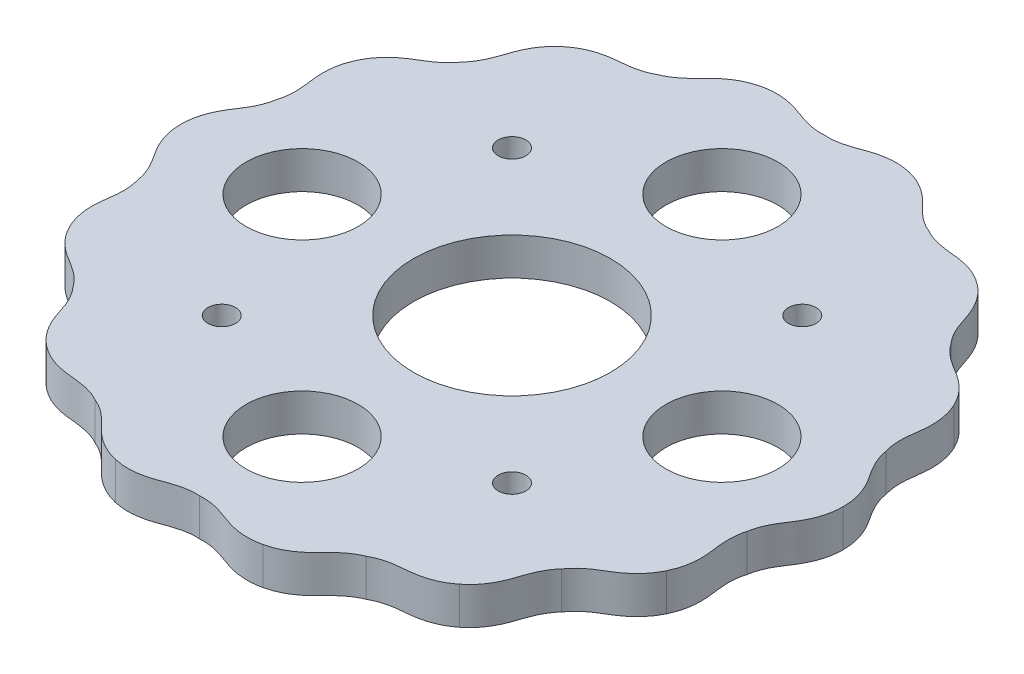
SolidWorks part; units mm, degrees
ref_plane "Front Plane" through (0, 0, 0) normal (0, 0, 1) x (1, 0, 0)
ref_plane "Top Plane" through (0, 0, 0) normal (0, 1, 0) x (1, 0, 0)
ref_plane "Right Plane" through (0, 0, 0) normal (1, 0, 0) x (0, 0, -1)
sketch "Sketch1" plane through (0, 0, 0) normal (0, 1, 0) x (1, 0, 0)
  line L0 (0, 0) -> (37.5, 0) construction
  line L1 (0, 0) -> (37.4807, 1.2019) construction
  line L2 (0, 0) -> (37.423, 2.4026) construction
  line L3 (0, 0) -> (37.3267, 3.6009) construction
  line L4 (0, 0) -> (37.1921, 4.7954) construction
  line L5 (0, 0) -> (37.0193, 5.985) construction
  line L6 (0, 0) -> (36.8085, 7.1684) construction
  line L7 (0, 0) -> (36.5598, 8.3445) construction
  line L8 (0, 0) -> (36.2736, 9.512) construction
  line L9 (0, 0) -> (35.95, 10.6698) construction
  line L10 (0, 0) -> (35.5896, 11.8166) construction
  line L11 (0, 0) -> (35.1926, 12.9512) construction
  line L12 (0, 0) -> (34.7594, 14.0725) construction
  line L13 (0, 0) -> (34.2905, 15.1794) construction
  line L14 (0, 0) -> (33.7863, 16.2706) construction
  line L15 (37.5, 0) -> (38.5, 0) construction
  line L16 (37.4807, 1.2019) -> (38.3521, 1.6927) construction
  line L17 (37.423, 2.4026) -> (37.9413, 3.2578) construction
  line L18 (37.3267, 3.6009) -> (37.3588, 4.6003) construction
  line L19 (37.1921, 4.7954) -> (36.7296, 5.682) construction
  line L20 (37.0193, 5.985) -> (36.1812, 6.5305) construction
  line L21 (36.8085, 7.1684) -> (35.8105, 7.2325) construction
  line L22 (36.5598, 8.3445) -> (35.5849, 8.122) construction
  line L23 (37, 0.0019) -> (37, 0)
  line L24 (33.3367, 16.052) -> (33.3358, 16.0537)
  line L25 (37, -0.0019) -> (37, 0)
  line L26 (33.3367, -16.052) -> (33.3358, -16.0537)
  line L27 (33.335, -16.0554) -> (33.3358, -16.0537)
  line L28 (23.0706, -28.9266) -> (23.0691, -28.9278)
  line L29 (23.0677, -28.9289) -> (23.0691, -28.9278)
  line L30 (8.2351, -36.0719) -> (8.2333, -36.0723)
  line L31 (8.2315, -36.0727) -> (8.2333, -36.0723)
  line L32 (-8.2315, -36.0727) -> (-8.2333, -36.0723)
  line L33 (-8.2351, -36.0719) -> (-8.2333, -36.0723)
  line L34 (-23.0677, -28.9289) -> (-23.0691, -28.9278)
  line L35 (-23.0706, -28.9266) -> (-23.0691, -28.9278)
  line L36 (-33.335, -16.0554) -> (-33.3358, -16.0537)
  line L37 (-33.3367, -16.052) -> (-33.3358, -16.0537)
  line L38 (-37, -0.0019) -> (-37, 0)
  line L39 (-37, 0.0019) -> (-37, 0)
  line L40 (-33.3367, 16.052) -> (-33.3358, 16.0537)
  line L41 (-33.335, 16.0554) -> (-33.3358, 16.0537)
  line L42 (-23.0706, 28.9266) -> (-23.0691, 28.9278)
  line L43 (-23.0677, 28.9289) -> (-23.0691, 28.9278)
  line L44 (-8.2351, 36.0719) -> (-8.2333, 36.0723)
  line L45 (-8.2315, 36.0727) -> (-8.2333, 36.0723)
  line L46 (8.2315, 36.0727) -> (8.2333, 36.0723)
  line L47 (8.2351, 36.0719) -> (8.2333, 36.0723)
  line L48 (23.0677, 28.9289) -> (23.0691, 28.9278)
  line L49 (23.0706, 28.9266) -> (23.0691, 28.9278)
  line L50 (33.335, 16.0554) -> (33.3358, 16.0537)
  line L51 (35.5, 0.0037) -> (35.5, 0)
  line L52 (31.986, 15.3995) -> (31.9844, 15.4029)
  line L53 (35.5, -0.0037) -> (35.5, 0)
  line L54 (31.986, -15.3995) -> (31.9844, -15.4029)
  line L55 (31.9828, -15.4062) -> (31.9844, -15.4029)
  line L56 (22.1368, -27.7527) -> (22.1339, -27.755)
  line L57 (22.131, -27.7573) -> (22.1339, -27.755)
  line L58 (7.9031, -34.6091) -> (7.8995, -34.6099)
  line L59 (7.8959, -34.6108) -> (7.8995, -34.6099)
  line L60 (-7.8959, -34.6108) -> (-7.8995, -34.6099)
  line L61 (-7.9031, -34.6091) -> (-7.8995, -34.6099)
  line L62 (-22.131, -27.7573) -> (-22.1339, -27.755)
  line L63 (-22.1368, -27.7527) -> (-22.1339, -27.755)
  line L64 (-31.9828, -15.4062) -> (-31.9844, -15.4029)
  line L65 (-31.986, -15.3995) -> (-31.9844, -15.4029)
  line L66 (-35.5, -0.0037) -> (-35.5, 0)
  line L67 (-35.5, 0.0037) -> (-35.5, 0)
  line L68 (-31.986, 15.3995) -> (-31.9844, 15.4029)
  line L69 (-31.9828, 15.4062) -> (-31.9844, 15.4029)
  line L70 (-22.1368, 27.7527) -> (-22.1339, 27.755)
  line L71 (-22.131, 27.7573) -> (-22.1339, 27.755)
  line L72 (-7.9031, 34.6091) -> (-7.8995, 34.6099)
  line L73 (-7.8959, 34.6108) -> (-7.8995, 34.6099)
  line L74 (7.8959, 34.6108) -> (7.8995, 34.6099)
  line L75 (7.9031, 34.6091) -> (7.8995, 34.6099)
  line L76 (22.131, 27.7573) -> (22.1339, 27.755)
  line L77 (22.1368, 27.7527) -> (22.1339, 27.755)
  line L78 (31.9828, 15.4062) -> (31.9844, 15.4029)
  circle A0 centre (0, 0) radius 35 construction
  circle A1 centre (37.5, 0) radius 2.5 construction
  circle A2 centre (0, 0) radius 37.5 construction
  spline S0 degree 3 poles (35.5849, 8.122) (35.6266, 7.5364) (36.0345, 6.7125) (36.7836, 5.6218) (37.4152, 4.5501) (38.2239, 2.702) (38.5014, 1.1074) (38.5, 0) knots 0 0 0 0 0.195516 0.310928 0.453873 0.621058 1 1 1 1
  spline S1 degree 3 poles (35.5849, 8.122) (35.3683, 8.6678) (35.3784, 9.5871) (35.5801, 10.8948) (35.6841, 12.1344) (35.611, 14.1503) (35.169, 15.7074) (34.6873, 16.7045) knots 0 0 0 0 0.195516 0.310928 0.453873 0.621058 1 1 1 1
  spline S2 degree 1 poles (34.1119, 7.7858) (33.3367, 16.052) knots 0 0 1 1 construction
  spline S3 degree 1 poles (34.1119, 7.7858) (37, 0.0019) knots 0 0 1 1 construction
  spline S4 degree 3 poles (33.3367, 16.052) (33.6005, 15.5058) (33.9037, 14.6401) (34.1146, 13.4372) (34.174, 12.5211) (34.1413, 11.5771) (34.0239, 10.6392) (33.8823, 9.6155) (33.9055, 8.625) (34.0243, 8.0514) (34.1119, 7.7858) knots 0.015853 0.015853 0.015853 0.015853 0.26189 0.384908 0.507927 0.630945 0.753963 0.876982 0.938491 1 1 1 1
  spline S5 degree 3 poles (34.1119, 7.7858) (34.1483, 7.5085) (34.2901, 6.9402) (34.6989, 6.0377) (35.2706, 5.1769) (35.7834, 4.3828) (36.2224, 3.5464) (36.5664, 2.6953) (36.8983, 1.52) (37.0008, 0.6085) (37, 0.0019) knots 0.015853 0.015853 0.015853 0.015853 0.077362 0.138872 0.26189 0.384908 0.507927 0.630945 0.753963 1 1 1 1
  spline S6 degree 3 poles (37, -0.0019) (37.0008, -0.6085) (36.8983, -1.52) (36.5664, -2.6953) (36.2224, -3.5464) (35.7834, -4.3828) (35.2706, -5.1769) (34.6989, -6.0377) (34.2901, -6.9402) (34.1483, -7.5085) (34.1119, -7.7858) knots 0.015853 0.015853 0.015853 0.015853 0.26189 0.384908 0.507927 0.630945 0.753963 0.876982 0.938491 1 1 1 1
  spline S7 degree 3 poles (34.1119, -7.7858) (34.0243, -8.0514) (33.9055, -8.625) (33.8823, -9.6155) (34.0239, -10.6392) (34.1413, -11.5771) (34.174, -12.5211) (34.1146, -13.4372) (33.9037, -14.6401) (33.6005, -15.5058) (33.3367, -16.052) knots 0.015853 0.015853 0.015853 0.015853 0.077362 0.138872 0.26189 0.384908 0.507927 0.630945 0.753963 1 1 1 1
  spline S8 degree 3 poles (33.335, -16.0554) (33.0725, -16.6022) (32.5847, -17.3791) (31.7758, -18.2939) (31.0965, -18.9115) (30.3381, -19.4746) (29.5316, -19.9675) (28.6429, -20.4951) (27.8831, -21.1308) (27.5087, -21.5813) (27.3556, -21.8154) knots 0.015853 0.015853 0.015853 0.015853 0.26189 0.384908 0.507927 0.630945 0.753963 0.876982 0.938491 1 1 1 1
  spline S9 degree 3 poles (27.3556, -21.8154) (27.1615, -22.0167) (26.8056, -22.4819) (26.3549, -23.3642) (26.0383, -24.348) (25.7371, -25.2439) (25.357, -26.1087) (24.906, -26.9083) (24.1941, -27.9005) (23.5453, -28.549) (23.0706, -28.9266) knots 0.015853 0.015853 0.015853 0.015853 0.077362 0.138872 0.26189 0.384908 0.507927 0.630945 0.753963 1 1 1 1
  spline S10 degree 3 poles (23.0677, -28.9289) (22.5939, -29.3077) (21.8173, -29.796) (20.6915, -30.2693) (19.8116, -30.531) (18.884, -30.7092) (17.9435, -30.8034) (16.9139, -30.8931) (15.9535, -31.1362) (15.4207, -31.3797) (15.1812, -31.5241) knots 0.015853 0.015853 0.015853 0.015853 0.26189 0.384908 0.507927 0.630945 0.753963 0.876982 0.938491 1 1 1 1
  spline S11 degree 3 poles (15.1812, -31.5241) (14.919, -31.6213) (14.3964, -31.886) (13.6076, -32.4854) (12.8955, -33.2344) (12.2354, -33.9109) (11.5177, -34.5251) (10.7645, -35.0499) (9.6926, -35.6349) (8.8266, -35.9377) (8.2351, -36.0719) knots 0.015853 0.015853 0.015853 0.015853 0.077362 0.138872 0.26189 0.384908 0.507927 0.630945 0.753963 1 1 1 1
  spline S12 degree 3 poles (8.2315, -36.0727) (7.6402, -36.2085) (6.7287, -36.3114) (5.5091, -36.2494) (4.6028, -36.1034) (3.6897, -35.8614) (2.8014, -35.5383) (1.8349, -35.1724) (0.8641, -34.9747) (0.2785, -34.9629) (0, -34.9891) knots 0.015853 0.015853 0.015853 0.015853 0.26189 0.384908 0.507927 0.630945 0.753963 0.876982 0.938491 1 1 1 1
  spline S13 degree 3 poles (0, -34.9891) (-0.2785, -34.9629) (-0.8641, -34.9747) (-1.8349, -35.1724) (-2.8014, -35.5383) (-3.6897, -35.8614) (-4.6028, -36.1034) (-5.5091, -36.2494) (-6.7287, -36.3114) (-7.6402, -36.2085) (-8.2315, -36.0727) knots 0.015853 0.015853 0.015853 0.015853 0.077362 0.138872 0.26189 0.384908 0.507927 0.630945 0.753963 1 1 1 1
  spline S14 degree 3 poles (-8.2351, -36.0719) (-8.8266, -35.9377) (-9.6926, -35.6349) (-10.7645, -35.0499) (-11.5177, -34.5251) (-12.2354, -33.9109) (-12.8955, -33.2344) (-13.6076, -32.4854) (-14.3964, -31.886) (-14.919, -31.6213) (-15.1812, -31.5241) knots 0.015853 0.015853 0.015853 0.015853 0.26189 0.384908 0.507927 0.630945 0.753963 0.876982 0.938491 1 1 1 1
  spline S15 degree 3 poles (-15.1812, -31.5241) (-15.4207, -31.3797) (-15.9535, -31.1362) (-16.9139, -30.8931) (-17.9435, -30.8034) (-18.884, -30.7092) (-19.8116, -30.531) (-20.6915, -30.2693) (-21.8173, -29.796) (-22.5939, -29.3077) (-23.0677, -28.9289) knots 0.015853 0.015853 0.015853 0.015853 0.077362 0.138872 0.26189 0.384908 0.507927 0.630945 0.753963 1 1 1 1
  spline S16 degree 3 poles (-23.0706, -28.9266) (-23.5453, -28.549) (-24.1941, -27.9005) (-24.906, -26.9083) (-25.357, -26.1087) (-25.7371, -25.2439) (-26.0383, -24.348) (-26.3549, -23.3642) (-26.8056, -22.4819) (-27.1615, -22.0167) (-27.3556, -21.8154) knots 0.015853 0.015853 0.015853 0.015853 0.26189 0.384908 0.507927 0.630945 0.753963 0.876982 0.938491 1 1 1 1
  spline S17 degree 3 poles (-27.3556, -21.8154) (-27.5087, -21.5813) (-27.8831, -21.1308) (-28.6429, -20.4951) (-29.5316, -19.9675) (-30.3381, -19.4746) (-31.0965, -18.9115) (-31.7758, -18.2939) (-32.5847, -17.3791) (-33.0725, -16.6022) (-33.335, -16.0554) knots 0.015853 0.015853 0.015853 0.015853 0.077362 0.138872 0.26189 0.384908 0.507927 0.630945 0.753963 1 1 1 1
  spline S18 degree 3 poles (-33.3367, -16.052) (-33.6005, -15.5058) (-33.9037, -14.6401) (-34.1146, -13.4372) (-34.174, -12.5211) (-34.1413, -11.5771) (-34.0239, -10.6392) (-33.8823, -9.6155) (-33.9055, -8.625) (-34.0243, -8.0514) (-34.1119, -7.7858) knots 0.015853 0.015853 0.015853 0.015853 0.26189 0.384908 0.507927 0.630945 0.753963 0.876982 0.938491 1 1 1 1
  spline S19 degree 3 poles (-34.1119, -7.7858) (-34.1483, -7.5085) (-34.2901, -6.9402) (-34.6989, -6.0377) (-35.2706, -5.1769) (-35.7834, -4.3828) (-36.2224, -3.5464) (-36.5664, -2.6953) (-36.8983, -1.52) (-37.0008, -0.6085) (-37, -0.0019) knots 0.015853 0.015853 0.015853 0.015853 0.077362 0.138872 0.26189 0.384908 0.507927 0.630945 0.753963 1 1 1 1
  spline S20 degree 3 poles (-37, 0.0019) (-37.0008, 0.6085) (-36.8983, 1.52) (-36.5664, 2.6953) (-36.2224, 3.5464) (-35.7834, 4.3828) (-35.2706, 5.1769) (-34.6989, 6.0377) (-34.2901, 6.9402) (-34.1483, 7.5085) (-34.1119, 7.7858) knots 0.015853 0.015853 0.015853 0.015853 0.26189 0.384908 0.507927 0.630945 0.753963 0.876982 0.938491 1 1 1 1
  spline S21 degree 3 poles (-34.1119, 7.7858) (-34.0243, 8.0514) (-33.9055, 8.625) (-33.8823, 9.6155) (-34.0239, 10.6392) (-34.1413, 11.5771) (-34.174, 12.5211) (-34.1146, 13.4372) (-33.9037, 14.6401) (-33.6005, 15.5058) (-33.3367, 16.052) knots 0.015853 0.015853 0.015853 0.015853 0.077362 0.138872 0.26189 0.384908 0.507927 0.630945 0.753963 1 1 1 1
  spline S22 degree 3 poles (-33.335, 16.0554) (-33.0725, 16.6022) (-32.5847, 17.3791) (-31.7758, 18.2939) (-31.0965, 18.9115) (-30.3381, 19.4746) (-29.5316, 19.9675) (-28.6429, 20.4951) (-27.8831, 21.1308) (-27.5087, 21.5813) (-27.3556, 21.8154) knots 0.015853 0.015853 0.015853 0.015853 0.26189 0.384908 0.507927 0.630945 0.753963 0.876982 0.938491 1 1 1 1
  spline S23 degree 3 poles (-27.3556, 21.8154) (-27.1615, 22.0167) (-26.8056, 22.4819) (-26.3549, 23.3642) (-26.0383, 24.348) (-25.7371, 25.2439) (-25.357, 26.1087) (-24.906, 26.9083) (-24.1941, 27.9005) (-23.5453, 28.549) (-23.0706, 28.9266) knots 0.015853 0.015853 0.015853 0.015853 0.077362 0.138872 0.26189 0.384908 0.507927 0.630945 0.753963 1 1 1 1
  spline S24 degree 3 poles (-23.0677, 28.9289) (-22.5939, 29.3077) (-21.8173, 29.796) (-20.6915, 30.2693) (-19.8116, 30.531) (-18.884, 30.7092) (-17.9435, 30.8034) (-16.9139, 30.8931) (-15.9535, 31.1362) (-15.4207, 31.3797) (-15.1812, 31.5241) knots 0.015853 0.015853 0.015853 0.015853 0.26189 0.384908 0.507927 0.630945 0.753963 0.876982 0.938491 1 1 1 1
  spline S25 degree 3 poles (-15.1812, 31.5241) (-14.919, 31.6213) (-14.3964, 31.886) (-13.6076, 32.4854) (-12.8955, 33.2344) (-12.2354, 33.9109) (-11.5177, 34.5251) (-10.7645, 35.0499) (-9.6926, 35.6349) (-8.8266, 35.9377) (-8.2351, 36.0719) knots 0.015853 0.015853 0.015853 0.015853 0.077362 0.138872 0.26189 0.384908 0.507927 0.630945 0.753963 1 1 1 1
  spline S26 degree 3 poles (-8.2315, 36.0727) (-7.6402, 36.2085) (-6.7287, 36.3114) (-5.5091, 36.2494) (-4.6028, 36.1034) (-3.6897, 35.8614) (-2.8014, 35.5383) (-1.8349, 35.1724) (-0.8641, 34.9747) (-0.2785, 34.9629) (0, 34.9891) knots 0.015853 0.015853 0.015853 0.015853 0.26189 0.384908 0.507927 0.630945 0.753963 0.876982 0.938491 1 1 1 1
  spline S27 degree 3 poles (0, 34.9891) (0.2785, 34.9629) (0.8641, 34.9747) (1.8349, 35.1724) (2.8014, 35.5383) (3.6897, 35.8614) (4.6028, 36.1034) (5.5091, 36.2494) (6.7287, 36.3114) (7.6402, 36.2085) (8.2315, 36.0727) knots 0.015853 0.015853 0.015853 0.015853 0.077362 0.138872 0.26189 0.384908 0.507927 0.630945 0.753963 1 1 1 1
  spline S28 degree 3 poles (8.2351, 36.0719) (8.8266, 35.9377) (9.6926, 35.6349) (10.7645, 35.0499) (11.5177, 34.5251) (12.2354, 33.9109) (12.8955, 33.2344) (13.6076, 32.4854) (14.3964, 31.886) (14.919, 31.6213) (15.1812, 31.5241) knots 0.015853 0.015853 0.015853 0.015853 0.26189 0.384908 0.507927 0.630945 0.753963 0.876982 0.938491 1 1 1 1
  spline S29 degree 3 poles (15.1812, 31.5241) (15.4207, 31.3797) (15.9535, 31.1362) (16.9139, 30.8931) (17.9435, 30.8034) (18.884, 30.7092) (19.8116, 30.531) (20.6915, 30.2693) (21.8173, 29.796) (22.5939, 29.3077) (23.0677, 28.9289) knots 0.015853 0.015853 0.015853 0.015853 0.077362 0.138872 0.26189 0.384908 0.507927 0.630945 0.753963 1 1 1 1
  spline S30 degree 3 poles (23.0706, 28.9266) (23.5453, 28.549) (24.1941, 27.9005) (24.906, 26.9083) (25.357, 26.1087) (25.7371, 25.2439) (26.0383, 24.348) (26.3549, 23.3642) (26.8056, 22.4819) (27.1615, 22.0167) (27.3556, 21.8154) knots 0.015853 0.015853 0.015853 0.015853 0.26189 0.384908 0.507927 0.630945 0.753963 0.876982 0.938491 1 1 1 1
  spline S31 degree 3 poles (27.3556, 21.8154) (27.5087, 21.5813) (27.8831, 21.1308) (28.6429, 20.4951) (29.5316, 19.9675) (30.3381, 19.4746) (31.0965, 18.9115) (31.7758, 18.2939) (32.5847, 17.3791) (33.0725, 16.6022) (33.335, 16.0554) knots 0.015853 0.015853 0.015853 0.015853 0.077362 0.138872 0.26189 0.384908 0.507927 0.630945 0.753963 1 1 1 1
  spline S32 degree 1 poles (32.6448, 7.451) (35.5, 0.0037) knots 0 0 1 1 construction
  spline S33 degree 1 poles (32.6448, 7.451) (31.986, 15.3995) knots 0 0 1 1 construction
  spline S34 degree 3 poles (35.5, 0.0037) (35.5006, 0.4959) (35.4183, 1.2336) (35.1496, 2.1927) (34.8707, 2.8896) (34.4997, 3.6015) (34.1394, 4.1652) (33.6939, 4.8394) (33.3068, 5.4873) (32.9751, 6.1975) (32.758, 6.8733) (32.6748, 7.2607) (32.6448, 7.451) knots 0.023011 0.023011 0.023011 0.023011 0.267258 0.389382 0.511505 0.633629 0.755753 0.816814 0.877876 0.938938 0.969469 1 1 1 1
  spline S35 degree 3 poles (32.6448, 7.451) (32.5893, 7.6354) (32.4961, 8.0206) (32.3985, 8.7236) (32.3893, 9.5074) (32.4569, 10.2591) (32.5657, 11.0598) (32.6458, 11.724) (32.6712, 12.5264) (32.6201, 13.2752) (32.446, 14.256) (32.2001, 14.9563) (31.986, 15.3995) knots 0.023011 0.023011 0.023011 0.023011 0.053542 0.084072 0.145134 0.206196 0.267258 0.389382 0.511505 0.633629 0.755753 1 1 1 1
  spline S36 degree 3 poles (32.6448, -7.451) (32.6748, -7.2607) (32.758, -6.8733) (32.9751, -6.1975) (33.3068, -5.4873) (33.6939, -4.8394) (34.1394, -4.1652) (34.4997, -3.6015) (34.8707, -2.8896) (35.1496, -2.1927) (35.4183, -1.2336) (35.5006, -0.4959) (35.5, -0.0037) knots 0.023011 0.023011 0.023011 0.023011 0.053542 0.084072 0.145134 0.206196 0.267258 0.389382 0.511505 0.633629 0.755753 1 1 1 1
  spline S37 degree 3 poles (31.986, -15.3995) (32.2001, -14.9563) (32.446, -14.256) (32.6201, -13.2752) (32.6712, -12.5264) (32.6458, -11.724) (32.5657, -11.0598) (32.4569, -10.2591) (32.3893, -9.5074) (32.3985, -8.7236) (32.4961, -8.0206) (32.5893, -7.6354) (32.6448, -7.451) knots 0.023011 0.023011 0.023011 0.023011 0.267258 0.389382 0.511505 0.633629 0.755753 0.816814 0.877876 0.938938 0.969469 1 1 1 1
  spline S38 degree 3 poles (26.1791, -20.8771) (26.2887, -20.7187) (26.5317, -20.4057) (27.0205, -19.8911) (27.6275, -19.3952) (28.2574, -18.9793) (28.9513, -18.5652) (29.5206, -18.2137) (30.1637, -17.7333) (30.7173, -17.2264) (31.3755, -16.4789) (31.7698, -15.8499) (31.9828, -15.4062) knots 0.023011 0.023011 0.023011 0.023011 0.053542 0.084072 0.145134 0.206196 0.267258 0.389382 0.511505 0.633629 0.755753 1 1 1 1
  spline S39 degree 3 poles (22.1368, -27.7527) (22.522, -27.4463) (23.0474, -26.922) (23.6297, -26.1139) (24.0007, -25.4614) (24.326, -24.7275) (24.542, -24.0943) (24.7914, -23.3257) (25.0566, -22.619) (25.405, -21.9169) (25.798, -21.3258) (26.0491, -21.0192) (26.1791, -20.8771) knots 0.023011 0.023011 0.023011 0.023011 0.267258 0.389382 0.511505 0.633629 0.755753 0.816814 0.877876 0.938938 0.969469 1 1 1 1
  spline S40 degree 3 poles (14.5283, -30.1683) (14.6957, -30.0732) (15.0505, -29.8966) (15.7143, -29.645) (16.4763, -29.4616) (17.2242, -29.3602) (18.0291, -29.2882) (18.6945, -29.2185) (19.4823, -29.0647) (20.201, -28.8482) (21.1184, -28.4603) (21.7465, -28.0647) (22.131, -27.7573) knots 0.023011 0.023011 0.023011 0.023011 0.053542 0.084072 0.145134 0.206196 0.267258 0.389382 0.511505 0.633629 0.755753 1 1 1 1
  spline S41 degree 3 poles (7.9031, -34.6091) (8.3831, -34.5002) (9.084, -34.2557) (9.9593, -33.7804) (10.5766, -33.3534) (11.1881, -32.8334) (11.6575, -32.3566) (12.2156, -31.7723) (12.7612, -31.2507) (13.3797, -30.7693) (13.9903, -30.4072) (14.3495, -30.2399) (14.5283, -30.1683) knots 0.023011 0.023011 0.023011 0.023011 0.267258 0.389382 0.511505 0.633629 0.755753 0.816814 0.877876 0.938938 0.969469 1 1 1 1
  spline S42 degree 3 poles (0, -33.4843) (0.1922, -33.4712) (0.5884, -33.4661) (1.2956, -33.5274) (2.0617, -33.6928) (2.7796, -33.926) (3.536, -34.2103) (4.1657, -34.4362) (4.9423, -34.6394) (5.6838, -34.7562) (6.6786, -34.8048) (7.4161, -34.7209) (7.8959, -34.6108) knots 0.023011 0.023011 0.023011 0.023011 0.053542 0.084072 0.145134 0.206196 0.267258 0.389382 0.511505 0.633629 0.755753 1 1 1 1
  spline S43 degree 3 poles (-7.8959, -34.6108) (-7.4161, -34.7209) (-6.6786, -34.8048) (-5.6838, -34.7562) (-4.9423, -34.6394) (-4.1657, -34.4362) (-3.536, -34.2103) (-2.7796, -33.926) (-2.0617, -33.6928) (-1.2956, -33.5274) (-0.5884, -33.4661) (-0.1922, -33.4712) (0, -33.4843) knots 0.023011 0.023011 0.023011 0.023011 0.267258 0.389382 0.511505 0.633629 0.755753 0.816814 0.877876 0.938938 0.969469 1 1 1 1
  spline S44 degree 3 poles (-14.5283, -30.1683) (-14.3495, -30.2399) (-13.9903, -30.4072) (-13.3797, -30.7693) (-12.7612, -31.2507) (-12.2156, -31.7723) (-11.6575, -32.3566) (-11.1881, -32.8334) (-10.5766, -33.3534) (-9.9593, -33.7804) (-9.084, -34.2557) (-8.3831, -34.5002) (-7.9031, -34.6091) knots 0.023011 0.023011 0.023011 0.023011 0.053542 0.084072 0.145134 0.206196 0.267258 0.389382 0.511505 0.633629 0.755753 1 1 1 1
  spline S45 degree 3 poles (-22.131, -27.7573) (-21.7465, -28.0647) (-21.1184, -28.4603) (-20.201, -28.8482) (-19.4823, -29.0647) (-18.6945, -29.2185) (-18.0291, -29.2882) (-17.2242, -29.3602) (-16.4763, -29.4616) (-15.7143, -29.645) (-15.0505, -29.8966) (-14.6957, -30.0732) (-14.5283, -30.1683) knots 0.023011 0.023011 0.023011 0.023011 0.267258 0.389382 0.511505 0.633629 0.755753 0.816814 0.877876 0.938938 0.969469 1 1 1 1
  spline S46 degree 3 poles (-26.1791, -20.8771) (-26.0491, -21.0192) (-25.798, -21.3258) (-25.405, -21.9169) (-25.0566, -22.619) (-24.7914, -23.3257) (-24.542, -24.0943) (-24.326, -24.7275) (-24.0007, -25.4614) (-23.6297, -26.1139) (-23.0474, -26.922) (-22.522, -27.4463) (-22.1368, -27.7527) knots 0.023011 0.023011 0.023011 0.023011 0.053542 0.084072 0.145134 0.206196 0.267258 0.389382 0.511505 0.633629 0.755753 1 1 1 1
  spline S47 degree 3 poles (-31.9828, -15.4062) (-31.7698, -15.8499) (-31.3755, -16.4789) (-30.7173, -17.2264) (-30.1637, -17.7333) (-29.5206, -18.2137) (-28.9513, -18.5652) (-28.2574, -18.9793) (-27.6275, -19.3952) (-27.0205, -19.8911) (-26.5317, -20.4057) (-26.2887, -20.7187) (-26.1791, -20.8771) knots 0.023011 0.023011 0.023011 0.023011 0.267258 0.389382 0.511505 0.633629 0.755753 0.816814 0.877876 0.938938 0.969469 1 1 1 1
  spline S48 degree 3 poles (-32.6448, -7.451) (-32.5893, -7.6354) (-32.4961, -8.0206) (-32.3985, -8.7236) (-32.3893, -9.5074) (-32.4569, -10.2591) (-32.5657, -11.0598) (-32.6458, -11.724) (-32.6712, -12.5264) (-32.6201, -13.2752) (-32.446, -14.256) (-32.2001, -14.9563) (-31.986, -15.3995) knots 0.023011 0.023011 0.023011 0.023011 0.053542 0.084072 0.145134 0.206196 0.267258 0.389382 0.511505 0.633629 0.755753 1 1 1 1
  spline S49 degree 3 poles (-35.5, -0.0037) (-35.5006, -0.4959) (-35.4183, -1.2336) (-35.1496, -2.1927) (-34.8707, -2.8896) (-34.4997, -3.6015) (-34.1394, -4.1652) (-33.6939, -4.8394) (-33.3068, -5.4873) (-32.9751, -6.1975) (-32.758, -6.8733) (-32.6748, -7.2607) (-32.6448, -7.451) knots 0.023011 0.023011 0.023011 0.023011 0.267258 0.389382 0.511505 0.633629 0.755753 0.816814 0.877876 0.938938 0.969469 1 1 1 1
  spline S50 degree 3 poles (-32.6448, 7.451) (-32.6748, 7.2607) (-32.758, 6.8733) (-32.9751, 6.1975) (-33.3068, 5.4873) (-33.6939, 4.8394) (-34.1394, 4.1652) (-34.4997, 3.6015) (-34.8707, 2.8896) (-35.1496, 2.1927) (-35.4183, 1.2336) (-35.5006, 0.4959) (-35.5, 0.0037) knots 0.023011 0.023011 0.023011 0.023011 0.053542 0.084072 0.145134 0.206196 0.267258 0.389382 0.511505 0.633629 0.755753 1 1 1 1
  spline S51 degree 3 poles (-31.986, 15.3995) (-32.2001, 14.9563) (-32.446, 14.256) (-32.6201, 13.2752) (-32.6712, 12.5264) (-32.6458, 11.724) (-32.5657, 11.0598) (-32.4569, 10.2591) (-32.3893, 9.5074) (-32.3985, 8.7236) (-32.4961, 8.0206) (-32.5893, 7.6354) (-32.6448, 7.451) knots 0.023011 0.023011 0.023011 0.023011 0.267258 0.389382 0.511505 0.633629 0.755753 0.816814 0.877876 0.938938 0.969469 1 1 1 1
  spline S52 degree 3 poles (-26.1791, 20.8771) (-26.2887, 20.7187) (-26.5317, 20.4057) (-27.0205, 19.8911) (-27.6275, 19.3952) (-28.2574, 18.9793) (-28.9513, 18.5652) (-29.5206, 18.2137) (-30.1637, 17.7333) (-30.7173, 17.2264) (-31.3755, 16.4789) (-31.7698, 15.8499) (-31.9828, 15.4062) knots 0.023011 0.023011 0.023011 0.023011 0.053542 0.084072 0.145134 0.206196 0.267258 0.389382 0.511505 0.633629 0.755753 1 1 1 1
  spline S53 degree 3 poles (-22.1368, 27.7527) (-22.522, 27.4463) (-23.0474, 26.922) (-23.6297, 26.1139) (-24.0007, 25.4614) (-24.326, 24.7275) (-24.542, 24.0943) (-24.7914, 23.3257) (-25.0566, 22.619) (-25.405, 21.9169) (-25.798, 21.3258) (-26.0491, 21.0192) (-26.1791, 20.8771) knots 0.023011 0.023011 0.023011 0.023011 0.267258 0.389382 0.511505 0.633629 0.755753 0.816814 0.877876 0.938938 0.969469 1 1 1 1
  spline S54 degree 3 poles (-14.5283, 30.1683) (-14.6957, 30.0732) (-15.0505, 29.8966) (-15.7143, 29.645) (-16.4763, 29.4616) (-17.2242, 29.3602) (-18.0291, 29.2882) (-18.6945, 29.2185) (-19.4823, 29.0647) (-20.201, 28.8482) (-21.1184, 28.4603) (-21.7465, 28.0647) (-22.131, 27.7573) knots 0.023011 0.023011 0.023011 0.023011 0.053542 0.084072 0.145134 0.206196 0.267258 0.389382 0.511505 0.633629 0.755753 1 1 1 1
  spline S55 degree 3 poles (-7.9031, 34.6091) (-8.3831, 34.5002) (-9.084, 34.2557) (-9.9593, 33.7804) (-10.5766, 33.3534) (-11.1881, 32.8334) (-11.6575, 32.3566) (-12.2156, 31.7723) (-12.7612, 31.2507) (-13.3797, 30.7693) (-13.9903, 30.4072) (-14.3495, 30.2399) (-14.5283, 30.1683) knots 0.023011 0.023011 0.023011 0.023011 0.267258 0.389382 0.511505 0.633629 0.755753 0.816814 0.877876 0.938938 0.969469 1 1 1 1
  spline S56 degree 3 poles (0, 33.4843) (-0.1922, 33.4712) (-0.5884, 33.4661) (-1.2956, 33.5274) (-2.0617, 33.6928) (-2.7796, 33.926) (-3.536, 34.2103) (-4.1657, 34.4362) (-4.9423, 34.6394) (-5.6838, 34.7562) (-6.6786, 34.8048) (-7.4161, 34.7209) (-7.8959, 34.6108) knots 0.023011 0.023011 0.023011 0.023011 0.053542 0.084072 0.145134 0.206196 0.267258 0.389382 0.511505 0.633629 0.755753 1 1 1 1
  spline S57 degree 3 poles (7.8959, 34.6108) (7.4161, 34.7209) (6.6786, 34.8048) (5.6838, 34.7562) (4.9423, 34.6394) (4.1657, 34.4362) (3.536, 34.2103) (2.7796, 33.926) (2.0617, 33.6928) (1.2956, 33.5274) (0.5884, 33.4661) (0.1922, 33.4712) (0, 33.4843) knots 0.023011 0.023011 0.023011 0.023011 0.267258 0.389382 0.511505 0.633629 0.755753 0.816814 0.877876 0.938938 0.969469 1 1 1 1
  spline S58 degree 3 poles (14.5283, 30.1683) (14.3495, 30.2399) (13.9903, 30.4072) (13.3797, 30.7693) (12.7612, 31.2507) (12.2156, 31.7723) (11.6575, 32.3566) (11.1881, 32.8334) (10.5766, 33.3534) (9.9593, 33.7804) (9.084, 34.2557) (8.3831, 34.5002) (7.9031, 34.6091) knots 0.023011 0.023011 0.023011 0.023011 0.053542 0.084072 0.145134 0.206196 0.267258 0.389382 0.511505 0.633629 0.755753 1 1 1 1
  spline S59 degree 3 poles (22.131, 27.7573) (21.7465, 28.0647) (21.1184, 28.4603) (20.201, 28.8482) (19.4823, 29.0647) (18.6945, 29.2185) (18.0291, 29.2882) (17.2242, 29.3602) (16.4763, 29.4616) (15.7143, 29.645) (15.0505, 29.8966) (14.6957, 30.0732) (14.5283, 30.1683) knots 0.023011 0.023011 0.023011 0.023011 0.267258 0.389382 0.511505 0.633629 0.755753 0.816814 0.877876 0.938938 0.969469 1 1 1 1
  spline S60 degree 3 poles (26.1791, 20.8771) (26.0491, 21.0192) (25.798, 21.3258) (25.405, 21.9169) (25.0566, 22.619) (24.7914, 23.3257) (24.542, 24.0943) (24.326, 24.7275) (24.0007, 25.4614) (23.6297, 26.1139) (23.0474, 26.922) (22.522, 27.4463) (22.1368, 27.7527) knots 0.023011 0.023011 0.023011 0.023011 0.053542 0.084072 0.145134 0.206196 0.267258 0.389382 0.511505 0.633629 0.755753 1 1 1 1
  spline S61 degree 3 poles (31.9828, 15.4062) (31.7698, 15.8499) (31.3755, 16.4789) (30.7173, 17.2264) (30.1637, 17.7333) (29.5206, 18.2137) (28.9513, 18.5652) (28.2574, 18.9793) (27.6275, 19.3952) (27.0205, 19.8911) (26.5317, 20.4057) (26.2887, 20.7187) (26.1791, 20.8771) knots 0.023011 0.023011 0.023011 0.023011 0.267258 0.389382 0.511505 0.633629 0.755753 0.816814 0.877876 0.938938 0.969469 1 1 1 1
  point P25 (0, 0)
  point P117 (0, 0)
  point P174 (0, 0)
  dimension "D1" = 70
  dimension "D2" = 5
  dimension "D4" = 25.714
  dimension "D5" = 1
  dimension "D7" = 180
  dimension "D8" = 207.551
  dimension "D6" = 1
  dimension "D9" = 1
  dimension "D10" = 235.102
  dimension "D11" = 1
  dimension "D12" = 1
  dimension "D13" = 1
  dimension "D14" = 1
  dimension "D15" = 1
  dimension "D16" = 262.653
  dimension "D17" = 290.204
  dimension "D18" = 317.755
  dimension "D19" = 345.306
  dimension "D20" = 1.5
  dimension "D22" = 3
  dimension "D3" = 15
  dimension "D21" = 14
  dimension "D23" = 14
extrude "Boss-Extrude3" add sketch "Sketch1" along normal blind 4 contours L51 L53 S36 S37 L54 L55 S38 S39 L56 L57 S40 S41 L58 L59 S42 S43 L60 L61 S44 S45 L62 L63 S46 S47 L64 L65 S48 S49 L66 L67 S50 S51 L68 L69 S52 S53 L70 L71 S54 S55 L72 L73 S56 S57 L74 L75 S58 S59 L76 L77 S60 S61 L78 L52 S35 S34
sketch "Sketch2" plane through (0, 4, 0) normal (0, 1, 0) x (1, 0, 0)
  line L0 (0, 0) -> (22.5, 0) construction
  line L1 (0, 0) -> (15.5563, 15.5563) construction
  circle A0 centre (0, 0) radius 10.5635
  circle A1 centre (22.5, 0) radius 6
  circle A6 centre (15.5563, 15.5563) radius 1.48
  circle A7 centre (0, -22.5) radius 6
  circle A8 centre (15.5563, -15.5563) radius 1.48
  circle A9 centre (-22.5, 0) radius 6
  circle A10 centre (-15.5563, -15.5563) radius 1.48
  circle A11 centre (0, 22.5) radius 6
  circle A12 centre (-15.5563, 15.5563) radius 1.48
  point P16 (0, 0)
  point P21 (0, 0)
  point P24 (0, 0)
  dimension "D3" = 12
  dimension "D1" = 21.127
  dimension "D6" = 2.96
  dimension "D2" = 22.5
  dimension "D4" = 45
  dimension "D5" = 22
  dimension "D7" = 4
extrude "Cut-Extrude1" cut sketch "Sketch2" against normal blind 5 contours A7 | A0 | A0 | A0 | L0 A0 | A0 L0 | A1 | A9 | A11 region at (0, 4, 0) region at (22.5, 4, 0) region at (0, 4, 22.5) region at (-22.5, 4, 0) region at (0, 4, -22.5)
extrude "Cut-Extrude2" cut sketch "Sketch2<4>" against normal blind 2.22 contours A12 | A10 | A8 | A6 region at (15.5563, 4, -15.5563) region at (15.5563, 4, 15.5563) region at (-15.5563, 4, 15.5563) region at (-15.5563, 4, -15.5563)
sketch "Sketch2<4>" plane through (0, 4, 0) normal (0, 1, 0) x (1, 0, 0) same geometry as "Sketch2"
equation "\"eccentricity\"= 1mm"
equation "\"Pin Diameter\"= 3mm"
equation "\"D5@Sketch1\" = \"eccentricity\""
equation "\"D6@Sketch1\" = \"eccentricity\""
equation "\"D9@Sketch1\" = \"eccentricity\""
equation "\"D11@Sketch1\" = \"eccentricity\""
equation "\"D12@Sketch1\" = \"eccentricity\""
equation "\"D14@Sketch1\" = \"eccentricity\""
equation "\"D13@Sketch1\" = \"eccentricity\""
equation "\"D15@Sketch1\" = \"eccentricity\""
equation "\"Disc Bearing Diameter\"=21"
equation "\"bearing_21_OD\"= 21mm"
equation "\"bearing_21_ID\"=15mm"
equation "\"pin_cirlce_diameter\"= 75mm"
equation "\"pin_diam\"= 6mm"
equation "\"gear_thickness\"= 4mm"
equation "\"ball_bearing_diam\"= 2.96mm"
equation "\"bearing_21_outer_clearance\"= 0.127mm'change this"
equation "\"bearing_21_inner_clearance\"=0mm'change this"
equation "\"bearing_15_OD\"= 15mm"
equation "\"bearing_15_ID\"=10mm"
equation "\"bearing_15_outer_clearance\"= 0mm'change this"
equation "\"bearing_15_inner_clearance\"= 0mm'change this"
equation "\"thrust_bearing_thickness\"= 5mm'measure this irl and change"
equation "\"D1@Sketch2\"=\"bearing_21_OD\"+\"bearing_21_outer_clearance\""
equation "\"D6@Sketch2\"=\"ball_bearing_diam\""
equation "\"D1@Cut-Extrude2\"=\"ball_bearing_diam\"*0.75"
